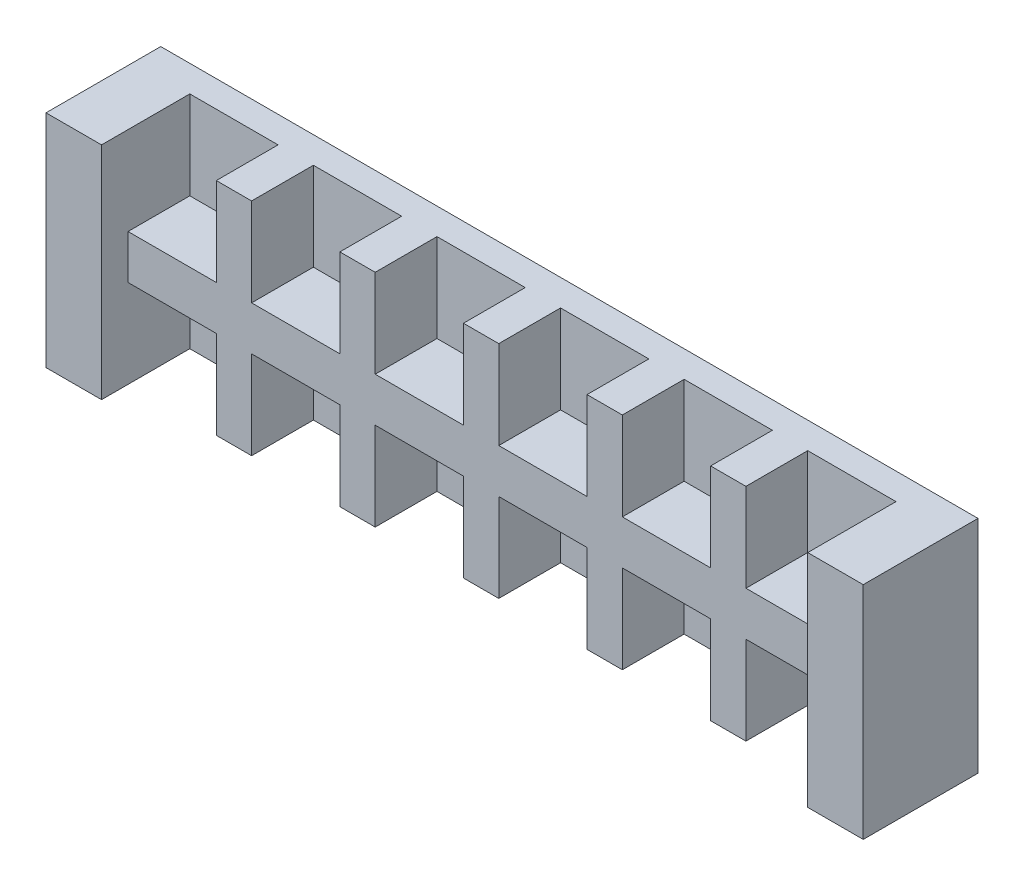
SolidWorks part; units mm, degrees
ref_plane "Front Plane" through (0, 0, 0) normal (0, 0, 1) x (1, 0, 0)
ref_plane "Top Plane" through (0, 0, 0) normal (0, 1, 0) x (1, 0, 0)
ref_plane "Right Plane" through (0, 0, 0) normal (1, 0, 0) x (0, 0, -1)
sketch "Sketch1" plane through (0, 0, 0) normal (0, 0, 1) x (1, 0, 0)
  line L1 (0, 0) -> (80, 0)
  line L2 (0, 0) -> (0, -25)
  line L3 (0, -25) -> (80, -25)
  line L4 (80, 0) -> (80, -25)
  dimension "D1" = 25
  dimension "D2" = 80
extrude "Boss-Extrude1" add sketch "Sketch1" along normal blind 10
sketch "Sketch3" plane through (0, 0, 10) normal (0, 0, 1) x (1, 0, 0)
  line L0 (80, 0) -> (0, 0) construction
  line L6 (30.2922, -10) -> (20.2922, -10)
  line L19 (60.2922, 0) -> (60.2922, -4.9649) construction
  line L20 (62.2922, 0) -> (72.2922, 0)
  line L21 (6.2922, 0) -> (16.2922, 0)
  line L22 (6.2922, 0) -> (6.2922, -10)
  line L23 (6.2922, -10) -> (16.2922, -10)
  line L24 (16.2922, 0) -> (16.2922, -10)
  line L25 (20.2922, 0) -> (20.2922, -10)
  line L26 (30.2922, 0) -> (20.2922, 0)
  line L27 (30.2922, 0) -> (30.2922, -10)
  line L28 (32.2922, 0) -> (32.2922, -6.155) construction
  line L29 (34.2922, 0) -> (34.2922, -10)
  line L30 (34.2922, 0) -> (44.2922, 0)
  line L31 (44.2922, 0) -> (44.2922, -10)
  line L32 (48.2922, 0) -> (48.2922, -10)
  line L33 (58.2922, -10) -> (48.2922, -10)
  line L34 (58.2922, 0) -> (58.2922, -10)
  line L35 (58.2922, 0) -> (48.2922, 0)
  line L36 (34.2922, -10) -> (44.2922, -10)
  line L37 (0, -12.5) -> (5.0077, -12.5) construction
  line L38 (0, 0) -> (0, -25) construction
  line L39 (34.2922, -15) -> (44.2922, -15)
  line L40 (58.2922, -25) -> (48.2922, -25)
  line L41 (58.2922, -25) -> (58.2922, -15)
  line L42 (58.2922, -15) -> (48.2922, -15)
  line L43 (48.2922, -25) -> (48.2922, -15)
  line L44 (44.2922, -25) -> (44.2922, -15)
  line L45 (34.2922, -25) -> (44.2922, -25)
  line L46 (34.2922, -25) -> (34.2922, -15)
  line L47 (32.2922, -25) -> (32.2922, -18.845) construction
  line L48 (30.2922, -25) -> (30.2922, -15)
  line L49 (30.2922, -25) -> (20.2922, -25)
  line L50 (20.2922, -25) -> (20.2922, -15)
  line L51 (16.2922, -25) -> (16.2922, -15)
  line L52 (6.2922, -15) -> (16.2922, -15)
  line L53 (6.2922, -25) -> (6.2922, -15)
  line L54 (6.2922, -25) -> (16.2922, -25)
  line L57 (30.2922, -15) -> (20.2922, -15)
  line L58 (62.2922, 0) -> (62.2922, -10)
  line L59 (62.2922, -10) -> (72.2922, -10)
  line L60 (72.2922, 0) -> (72.2922, -10)
  line L61 (72.2922, -25) -> (72.2922, -15)
  line L62 (62.2922, -15) -> (72.2922, -15)
  line L63 (62.2922, -25) -> (62.2922, -15)
  line L64 (62.2922, -25) -> (72.2922, -25)
  dimension "D1" = 2
  dimension "D2" = 2
extrude "Cut-Extrude1" cut sketch "Sketch3<2>" against normal blind 7 contours L23 L24 L21 L22
sketch "Sketch3<2>" plane through (0, 0, 10) normal (0, 0, 1) x (1, 0, 0) same geometry as "Sketch3"
extrude "Cut-Extrude2" cut sketch "Sketch3<3>" against normal blind 7 contours L6 L25 L26 L27
sketch "Sketch3<3>" plane through (0, 0, 10) normal (0, 0, 1) x (1, 0, 0) same geometry as "Sketch3"
extrude "Cut-Extrude3" cut sketch "Sketch3" against normal blind 7 contours L36 L31 L30 L29
extrude "Cut-Extrude4" cut sketch "Sketch3<6>" against normal blind 7 contours L32 L33 L34 L35
sketch "Sketch3<6>" plane through (0, 0, 10) normal (0, 0, 1) x (1, 0, 0) same geometry as "Sketch3"
extrude "Cut-Extrude5" cut sketch "Sketch3<7>" against normal blind 7 contours L58 L59 L60 L20
sketch "Sketch3<7>" plane through (0, 0, 10) normal (0, 0, 1) x (1, 0, 0) same geometry as "Sketch3"
extrude "Cut-Extrude6" cut sketch "Sketch3<8>" against normal blind 7 contours L63 L62 L61 L64
sketch "Sketch3<8>" plane through (0, 0, 10) normal (0, 0, 1) x (1, 0, 0) same geometry as "Sketch3"
extrude "Cut-Extrude7" cut sketch "Sketch3<9>" against normal blind 7 contours L43 L42 L41 L40
sketch "Sketch3<9>" plane through (0, 0, 10) normal (0, 0, 1) x (1, 0, 0) same geometry as "Sketch3"
extrude "Cut-Extrude8" cut sketch "Sketch3<10>" against normal blind 7 contours L46 L39 L44 L45
sketch "Sketch3<10>" plane through (0, 0, 10) normal (0, 0, 1) x (1, 0, 0) same geometry as "Sketch3"
extrude "Cut-Extrude9" cut sketch "Sketch3<11>" against normal blind 7 contours L50 L57 L48 L49
sketch "Sketch3<11>" plane through (0, 0, 10) normal (0, 0, 1) x (1, 0, 0) same geometry as "Sketch3"
extrude "Cut-Extrude10" cut sketch "Sketch3<12>" against normal blind 7 contours L53 L52 L51 L54
sketch "Sketch3<12>" plane through (0, 0, 10) normal (0, 0, 1) x (1, 0, 0) same geometry as "Sketch3"
sketch "Sketch4" plane through (0, 0, 10) normal (0, 0, 1) x (1, 0, 0)
  line L0 (74.2922, 0) -> (74.2922, -4.3688) construction
  line L1 (80, 0) -> (72.2922, 0) construction
  line L2 (72.2922, 0) -> (72.2922, -10) construction
  line L3 (72.2922, -25) -> (80, -25) construction
  line L4 (76.2922, 0) -> (92.5822, 0)
  line L5 (76.2922, 0) -> (76.2922, -25)
  line L6 (76.2922, -25) -> (92.5822, -25)
  line L7 (92.5822, 0) -> (92.5822, -25)
  line L9 (16.2922, -10) -> (0, -10) construction
  line L10 (0, 0) -> (0, -25) construction
  dimension "D1" = 2
  dimension "D2" = 2
  dimension "D3" = 16.29
extrude "Boss-Extrude2" add sketch "Sketch4" against normal up to surface (10 mm away) contours L6 L7 L4 L5 up to face at (40, -12.5, 0)
sketch "Sketch5" plane through (0, 0, 10) normal (0, 0, 1) x (1, 0, 0)
  line L0 (92.5822, 0) -> (72.2922, 0) construction
  line L1 (76.2922, 0) -> (86.2922, 0)
  line L2 (76.2922, 0) -> (76.2922, -10)
  line L3 (76.2922, -10) -> (86.2922, -10)
  line L4 (86.2922, 0) -> (86.2922, -10)
  line L5 (72.2922, -25) -> (92.5822, -25) construction
  line L6 (76.2922, -15) -> (86.2922, -15)
  line L7 (76.2922, -15) -> (76.2922, -25)
  line L8 (76.2922, -25) -> (86.2922, -25)
  line L9 (86.2922, -15) -> (86.2922, -25)
  line L10 (72.2922, 0) -> (72.2922, -10) construction
  line L11 (72.2922, -25) -> (72.2922, -15) construction
  point P14 (72.2922, -5)
  dimension "D1" = 10
  dimension "D2" = 10
  dimension "D3" = 4
  dimension "D4" = 10
  dimension "D5" = 10
  dimension "D6" = 4
extrude "Cut-Extrude12" cut sketch "Sketch5" against normal blind 7
sketch "Sketch6" plane through (0, 0, 10) normal (0, 0, 1) x (1, 0, 0)
  line L1 (0, 0) -> (6.2922, 0)
  line L2 (0, 0) -> (0, -25)
  line L3 (0, -25) -> (6.2922, -25)
  line L4 (6.2922, 0) -> (6.2922, -25)
  line L5 (86.2922, 0) -> (92.5822, 0)
  line L6 (86.2922, 0) -> (86.2922, -25)
  line L7 (86.2922, -25) -> (92.5822, -25)
  line L8 (92.5822, 0) -> (92.5822, -25)
extrude "Boss-Extrude3" add sketch "Sketch6" along normal blind 3
sketch "Sketch7" plane through (0, 0, 13) normal (0, 0, 1) x (1, 0, 0)
  line L0 (0, 0) -> (0, -25) construction
  line L1 (0, 0) -> (92.5822, 0) construction
equation "\"e\"=7"
